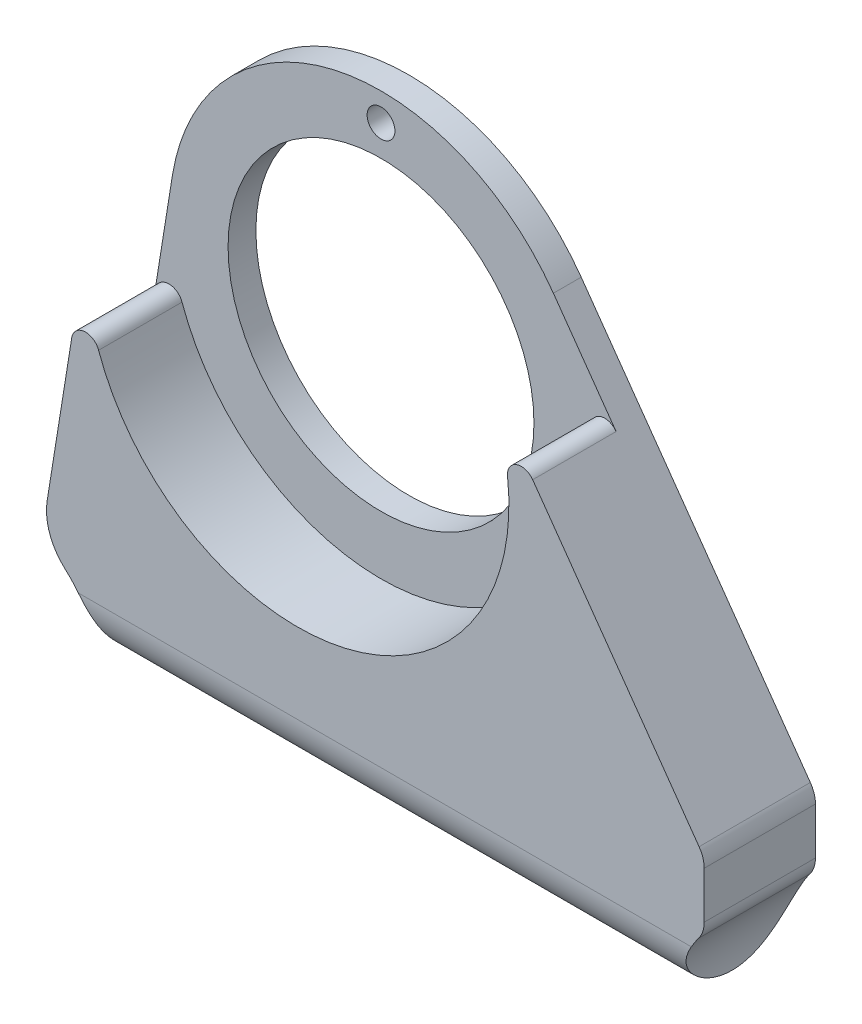
SolidWorks part; units mm, degrees
ref_plane "前视基准面" through (0, 0, 0) normal (0, 0, 1) x (1, 0, 0)
ref_plane "上视基准面" through (0, 0, 0) normal (0, 1, 0) x (1, 0, 0)
ref_plane "右视基准面" through (0, 0, 0) normal (1, 0, 0) x (0, 0, -1)
other "Configuration Table"
sketch "草图1" plane through (0, 0, 0) normal (0, 0, 1) x (1, 0, 0)
  circle A0 centre (0, 0) radius 38
  circle A1 centre (0, 0) radius 33 construction
  circle A2 centre (0, 33) radius 2.5
  circle A3 centre (0, 0) radius 27.5
  dimension "D1" = 76
  dimension "D2" = 66
  dimension "D3" = 5
  dimension "D4" = 55
extrude "凸台-拉伸1" add sketch "草图1" along normal blind 5
sketch "草图2" plane through (0, 0, 0) normal (0, 0, -1) x (-1, 0, 0)
  line L0 (-30.995, 21.9843) -> (-73.1164, -37.4014)
  line L1 (-73.1164, -37.4014) -> (-73.1164, -52.3924)
  line L2 (-73.1164, -52.3924) -> (46.8836, -52.3924)
  line L3 (46.8836, -52.3924) -> (37.521, 6.0146)
  circle A0 centre (0, 0) radius 38 construction
  arc A1 (-30.995, 21.9843) -> (37.521, 6.0146) centre (0, 0) ccw
  dimension "D1" = 120
extrude "凸台-拉伸2" add sketch "草图2" against normal blind 20
fillet "圆角2" radius 2.5 2 edges at (30.995, 21.9843, 12.5) (-37.521, 6.0146, 12.5)
fillet "圆角3" radius 10 1 edges at (-46.8836, -52.3924, 10)
fillet "圆角4" radius 5 2 edges at (73.1164, -52.3924, 10) (73.1164, -37.4014, 10)
sketch "草图3" plane through (0, -52.3924, 0) normal (0, -1, 0) x (1, 0, 0)
  line L0 (68.1164, 0) -> (68.1164, 20) construction
  line L1 (-35.153, 20) -> (68.1164, 20)
  line L2 (-35.153, 20) -> (-35.153, 10)
  line L3 (-35.153, 10) -> (68.1164, 10)
  line L4 (68.1164, 20) -> (68.1164, 10)
revolve "旋转1" add sketch "草图3" angle 180 about L3
fillet "圆角6" radius 20 2 edges at (68.1164, -52.3924, 10) (-35.153, -52.3924, 10)
ref_plane "基准面1" through (0, 0, 10) normal (0, 0, 1) x (1, 0, 0)
